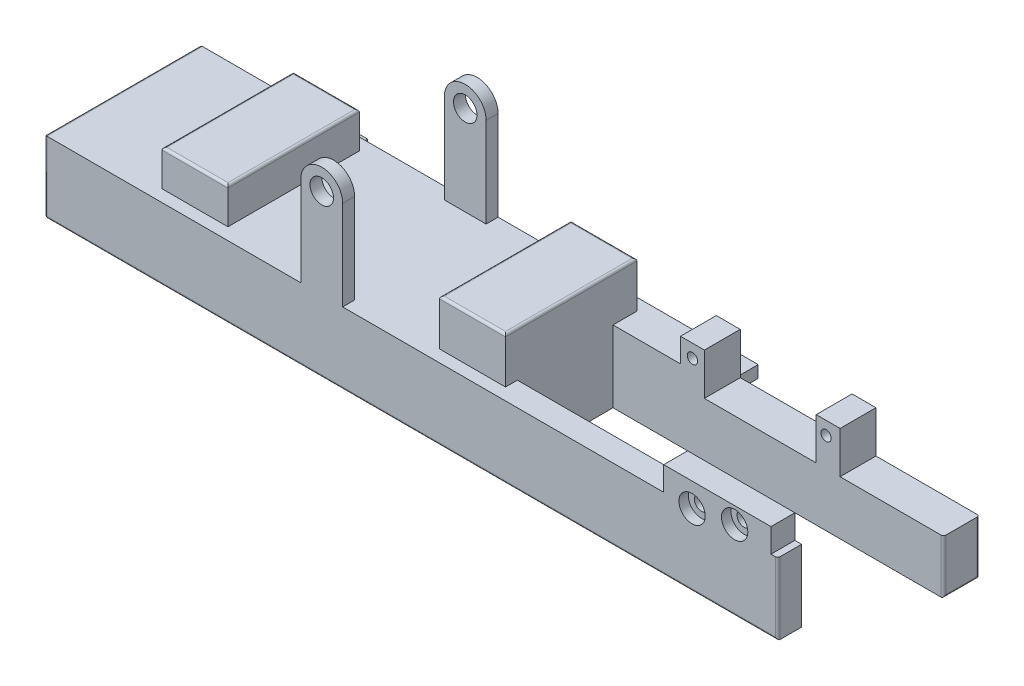
SolidWorks part; units mm, degrees
other "Markup1"
sketch "Sketch17" plane through (106.68, 38.735, 16.51) normal (0.2565, 0.8765, 0.4073) x (0.8462, 0, -0.5329)
ref_plane "Front" through (0, 0, 0) normal (0, 0, 1) x (1, 0, 0)
ref_plane "Top" through (0, 0, 0) normal (0, 1, 0) x (1, 0, 0)
ref_plane "Right" through (0, 0, 0) normal (1, 0, 0) x (0, 0, -1)
sketch "Sketch1" plane through (0, 0, 0) normal (0, 1, 0) x (1, 0, 0)
  line L0 (-58.8676, 16.51) -> (-58.8676, -16.51)
  line L1 (-106.68, 16.51) -> (106.68, 16.51)
  line L2 (-106.68, 16.51) -> (-106.68, -16.51)
  line L3 (-106.68, -16.51) -> (106.68, -16.51)
  line L4 (106.68, 16.51) -> (106.68, -16.51)
  line L5 (-106.68, 16.51) -> (106.68, -16.51) construction
  line L6 (-106.68, -16.51) -> (106.68, 16.51) construction
  line L7 (106.68, -16.51) -> (55.88, -16.51)
  line L8 (106.68, -16.51) -> (106.68, 8.89)
  line L9 (106.68, 8.89) -> (55.88, 8.89)
  line L10 (55.88, -16.51) -> (55.88, 8.89)
  line L11 (0, -55) -> (0, 55) construction
  line L12 (36.4884, 16.51) -> (46.4884, 16.51)
  line L13 (36.4884, 16.51) -> (36.4884, 29.718)
  line L14 (36.4884, 29.718) -> (46.4884, 29.718)
  line L15 (46.4884, 16.51) -> (46.4884, 29.718)
  line L16 (-36.4884, 29.718) -> (-46.4884, 29.718)
  line L17 (-46.4884, 16.51) -> (-46.4884, 29.718)
  line L18 (-36.4884, 16.51) -> (-46.4884, 16.51)
  line L19 (-36.4884, 16.51) -> (-36.4884, 29.718)
  line L21 (55.88, -16.51) -> (96.8527, -16.51)
  line L22 (55.88, -16.51) -> (55.88, -11.43)
  line L23 (55.88, -11.43) -> (96.8527, -11.43)
  line L24 (96.8527, -16.51) -> (96.8527, -11.43)
  circle A0 centre (-41.4884, 20.01) radius 2
  circle A1 centre (41.4884, 20.01) radius 2
  point P0 (0, 0)
  dimension "D7" = 4
  dimension "D1" = 213.36
  dimension "D2" = 33.02
  dimension "D3" = 25.4
  dimension "D4" = 50.8
  dimension "D5" = 10
  dimension "D6" = 13.208
  dimension "D8" = 5.08
extrude "Boss-Extrude1" add sketch "Sketch1" along normal blind 15.24 contours L3 L10 L9 L4 L1 L0 | L3 L24 L23 L10 region at (6.1788, 0, -1.1772) region at (76.3663, 0, 13.97)
sketch "Sketch3" plane through (0, 0, 16.51) normal (0, 0, 1) x (1, 0, 0)
  line L0 (4.445, 15.24) -> (-4.445, 15.24)
  line L1 (-58.8676, 15.24) -> (96.8527, 15.24) construction
  line L2 (-4.445, 15.24) -> (-4.445, 34.29)
  line L3 (4.445, 15.24) -> (4.445, 34.29)
  line L4 (0, -55) -> (0, 55) construction
  arc A0 (-4.445, 34.29) -> (4.445, 34.29) centre (0, 34.29) cw
  circle A1 centre (0, 34.29) radius 2.5
  point P8 (0, 15.24)
  dimension "D2" = 5
  dimension "D1" = 8.89
  dimension "D3" = 19.05
extrude "Boss-Extrude2" add sketch "Sketch3" against normal blind 2.54
mirror "Mirror1" about plane through (0, 0, 0) normal (0, 0, 1) of "Boss-Extrude2"
sketch "Sketch4" plane through (0, 15.24, 0) normal (0, 1, 0) x (1, 0, 0)
  line L0 (-21.3042, 0) -> (21.3042, 0) construction
  line L1 (22.4759, 13.9568) -> (36.4759, 13.9568)
  line L2 (22.4759, 13.9568) -> (22.4759, -13.9568)
  line L3 (22.4759, -13.9568) -> (36.4759, -13.9568)
  line L4 (36.4759, 13.9568) -> (36.4759, -13.9568)
  line L5 (0, -18.161) -> (0, 18.161) construction
  line L6 (-22.4759, -13.9568) -> (-36.4759, -13.9568)
  line L7 (-36.4759, 13.9568) -> (-36.4759, -13.9568)
  line L8 (-22.4759, 13.9568) -> (-36.4759, 13.9568)
  line L9 (-22.4759, 13.9568) -> (-22.4759, -13.9568)
  line L10 (-29.4759, 13.9568) -> (-29.4759, -13.9568) construction
  line L11 (29.4759, 13.9568) -> (29.4759, -13.9568) construction
  point P4 (22.4759, 0)
  dimension "D1" = 14
  dimension "D2" = 58.9518
extrude "Boss-Extrude3" add sketch "Sketch4" along normal blind 7.62
sketch "Sketch11" plane through (0, 22.86, 0) normal (0, 1, 0) x (1, 0, 0)
  line L4 (-36.4759, -13.9568) -> (-22.4759, -13.9568)
  line L5 (-36.4759, 13.9568) -> (-36.4759, -13.9568)
  line L6 (-22.4759, 13.9568) -> (-36.4759, 13.9568)
  line L7 (-22.4759, -13.9568) -> (-22.4759, 13.9568)
  line L8 (-36.4759, -13.9568) -> (-22.4759, -13.9568)
  line L9 (-36.4759, 13.9568) -> (-36.4759, -13.9568)
  line L10 (-22.4759, 13.9568) -> (-36.4759, 13.9568)
  line L11 (-22.4759, -13.9568) -> (-22.4759, 13.9568)
  line L12 (36.4759, 13.9568) -> (22.4759, 13.9568)
  line L13 (36.4759, -13.9568) -> (36.4759, 13.9568)
  line L14 (22.4759, -13.9568) -> (36.4759, -13.9568)
  line L15 (22.4759, 13.9568) -> (22.4759, -13.9568)
  line L16 (36.4759, 13.9568) -> (22.4759, 13.9568)
  line L17 (36.4759, -13.9568) -> (36.4759, 13.9568)
  line L18 (22.4759, -13.9568) -> (36.4759, -13.9568)
  line L19 (22.4759, 13.9568) -> (22.4759, -13.9568)
  dimension "D1" = 0
  dimension "D2" = 0
extrude "Boss-Extrude6" add sketch "Sketch11" along normal blind 2.0955 contours L16 L19 L18 L17
sketch "Sketch6" plane through (0, 22.86, 0) normal (0, 1, 0) x (1, 0, 0)
  line L1 (36.4759, 13.9568) -> (22.4759, 13.9568) construction
  line L4 (-22.4759, -13.9568) -> (-22.4759, 13.9568)
  line L5 (-22.4759, 13.9568) -> (-36.4759, 13.9568)
  line L6 (-36.4759, 13.9568) -> (-36.4759, -13.9568)
  line L7 (-36.4759, -13.9568) -> (-22.4759, -13.9568)
  line L8 (-22.4759, -13.9568) -> (-22.4759, 13.9568)
  line L9 (-22.4759, 13.9568) -> (-36.4759, 13.9568)
  line L10 (-36.4759, 13.9568) -> (-36.4759, -13.9568)
  line L11 (-36.4759, -13.9568) -> (-22.4759, -13.9568)
  circle A4 centre (-29.4759, 6.5433) radius 5.5
  circle A5 centre (29.4759, 6.5433) radius 5.5
  point P8 (-29.4759, 13.9568)
  point P14 (29.4759, 13.9568)
  dimension "D3" = 11
  dimension "D2" = 11
  dimension "D1" = 0
extrude "Cut-Extrude1" cut sketch "Sketch6" against normal blind 3 from offset 1.5 contours A4 offset against normal yes
fillet "Fillet1" radius 0.508 18 edges at (-58.8676, 15.24, 0) (-58.8676, 0, 0) (106.68, 0, -12.7) (106.68, 7.62, -8.89) (106.68, 7.62, -16.51) (-58.8676, 7.62, -16.51) (-58.8676, 7.62, 16.51) (18.9925, 0, 16.51) (-29.4759, 22.86, 13.9568) (-36.4759, 22.86, 0) (-29.4759, 22.86, -13.9568) (-22.4759, 22.86, 0) (29.4759, 24.9555, 13.9568) (22.4759, 24.9555, 0) (29.4759, 24.9555, -13.9568) (36.4759, 24.9555, 0) (106.68, 15.24, -12.7) (96.8527, 7.62, 16.51)
sketch "Sketch8" plane through (0, 15.24, 0) normal (0, 1, 0) x (1, 0, 0)
  line L0 (36.4759, 13.9568) -> (36.4759, -13.9568) construction
  line L1 (58.1514, 8.382) -> (58.1514, -16.002)
  line L3 (56.4759, 8.89) -> (36.4759, 8.89)
  line L4 (56.4759, 8.89) -> (56.4759, -11.43)
  line L5 (56.4759, -11.43) -> (36.4759, -11.43)
  line L6 (36.4759, 8.89) -> (36.4759, -11.43)
  line M44 (55.88, -11.43) -> (55.88, 8.89)
  line M46 (96.8527, -11.43) -> (55.88, -11.43)
  dimension "D1" = 20.32
  dimension "D3" = 20
extrude "Cut-Extrude2" cut sketch "Sketch8" against normal through all contours L3 L6 L5 L4 M46 M44 region at (46.178, 15.24, 1.27)
extrude "Boss-Extrude5" add sketch "Sketch1<3>" along normal blind 2.54 contours L1 L15 L14 L13 | L1 L19 L16 L17 region at (-41.4884, 0, -23.4404) region at (41.4884, 0, -23.4404)
sketch "Sketch1<3>" plane through (0, 0, 0) normal (0, 1, 0) x (1, 0, 0) same geometry as "Sketch1"
sketch "Sketch14" plane through (0, 0, -8.89) normal (0, 0, 1) x (1, 0, 0)
  line L0 (106.172, 15.24) -> (36.4759, 15.24) construction
  line L2 (106.68, 15.24) -> (106.68, 11.43)
  line L3 (106.68, 11.43) -> (55.88, 11.43)
  line L4 (55.88, 15.24) -> (55.88, 11.43)
  line L5 (106.68, 14.732) -> (106.68, 0.508) construction
  line L6 (55.88, 15.24) -> (106.68, 15.24)
  dimension "D1" = 3.81
  dimension "D4" = 50.8
extrude "Cut-Extrude5" cut sketch "Sketch14" against normal through all and the other way blind 9.2075
sketch "Sketch15" plane through (0, 0, -8.89) normal (0, 0, 1) x (1, 0, 0)
  line L0 (55.88, 15.24) -> (36.4759, 15.24) construction
  line L1 (50.8, 15.24) -> (55.88, 15.24)
  line L2 (50.8, 15.24) -> (50.8, 20.32)
  line L3 (50.8, 20.32) -> (55.88, 20.32)
  line L4 (55.88, 15.24) -> (55.88, 20.32)
  line L5 (106.172, 11.43) -> (55.88, 11.43) construction
  line L6 (79.629, 11.43) -> (84.709, 11.43)
  line L7 (79.629, 11.43) -> (79.629, 20.32)
  line L8 (79.629, 20.32) -> (84.709, 20.32)
  line L9 (84.709, 11.43) -> (84.709, 20.32)
  line L11 (55.88, 11.43) -> (55.88, 15.24) construction
  dimension "D1" = 5.08
  dimension "D2" = 23.749
  dimension "D3" = 5.08
  dimension "D4" = 5.08
extrude "Boss-Extrude7" add sketch "Sketch15" against normal up to vertex (7.62 mm away) up to point (55.88, 15.24, -16.51)
sketch "Sketch16" plane through (0, 0, -8.89) normal (0, 0, 1) x (1, 0, 0)
  line L0 (55.88, 11.43) -> (55.88, 20.32) construction
  line L1 (106.172, 11.43) -> (84.709, 11.43) construction
  circle A0 centre (53.34, 17.526) radius 1.0922
  circle A1 centre (81.7245, 17.526) radius 1.0922
  dimension "D1" = 2.1844
  dimension "D2" = 2.54
  dimension "D3" = 6.096
  dimension "D4" = 28.3845
extrude "Cut-Extrude6" cut sketch "Sketch16" against normal up to next
sketch "Sketch18" plane through (0, 15.24, 0) normal (0, 1, 0) x (1, 0, 0)
  line L0 (36.4759, -11.43) -> (96.8527, -11.43) construction
  line L1 (95.4237, -11.43) -> (72.6409, -11.43)
  line L2 (95.4237, -11.43) -> (95.4237, -16.51)
  line L3 (95.4237, -16.51) -> (72.6409, -16.51)
  line L4 (72.6409, -11.43) -> (72.6409, -16.51)
  line L5 (4.445, -16.51) -> (96.3447, -16.51) construction
extrude "Boss-Extrude8" add sketch "Sketch18" along normal blind 5.08
sketch "Sketch9" plane through (0, 0, 11.43) normal (0, 0, -1) x (-1, 0, 0)
  line L0 (-87.7134, 16.8367) -> (-78.6583, 15.24) construction
  line L2 (18.161, 0) -> (-18.161, 0) construction
  circle A0 centre (-87.7134, 16.8367) radius 1.4986
  circle A1 centre (-78.6583, 15.24) radius 1.4986
  dimension "D1" = 2.9972
  dimension "D4" = 15.24
  dimension "D2" = 9.1948
  dimension "D3" = 10
extrude "Cut-Extrude3" cut sketch "Sketch9" along normal blind 12.7 and the other way blind 12.7
sketch "Sketch10" plane through (0, 0, 16.51) normal (0, 0, 1) x (1, 0, 0)
  circle A0 centre (78.6583, 15.24) radius 2.794
  circle A1 centre (87.7134, 16.8367) radius 2.794
  circle M2 centre (87.7134, 16.8367) radius 1.4986
  circle M3 centre (78.6583, 15.24) radius 1.4986
  dimension "D1" = 5.588
extrude "Cut-Extrude4" cut sketch "Sketch10" against normal blind 2 contours A0 M3 | A1 M2 region at (75.9434, 15.24, 16.51) region at (84.9985, 16.8367, 16.51)
sketch "Sketch19" plane through (0, 24.9555, 0) normal (0, 1, 0) x (1, 0, 0)
  line L0 (36.4759, 13.9568) -> (22.4759, 13.9568) construction
  line L1 (36.4759, 13.9568) -> (22.4759, 13.9568)
  circle A0 centre (29.4759, 6.5433) radius 5.5
  circle A1 centre (-29.4759, 6.5433) radius 5.5 construction
  circle A2 centre (-29.4759, 6.5433) radius 5.5
  point P5 (0, 0)
  point P8 (29.4759, 13.9568)
extrude "Cut-Extrude7" cut sketch "Sketch19" against normal blind 3.5 from offset 1 contours A0 offset against normal yes
